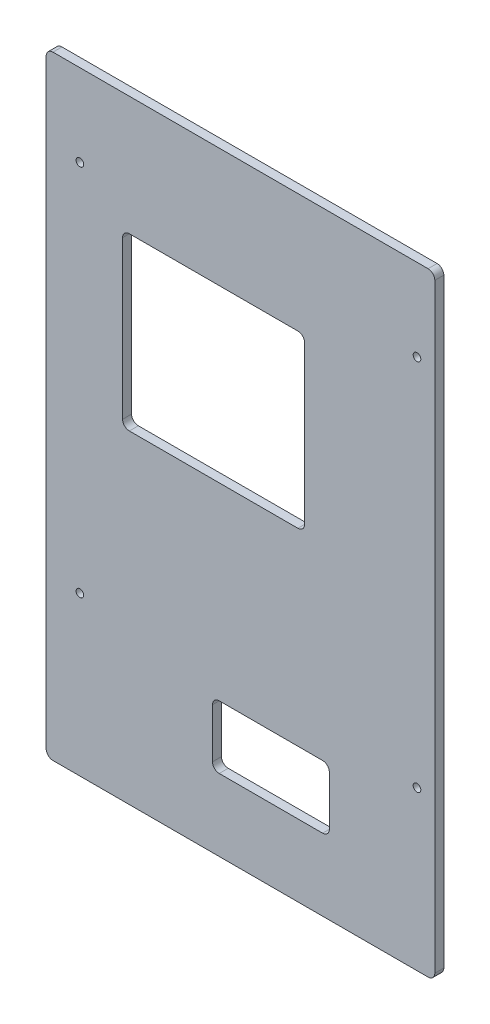
SolidWorks part; units mm, degrees
material "Verre"
ref_plane "Plan de face" through (0, 0, 0) normal (0, 0, 1) x (1, 0, 0)
ref_plane "Plan de dessus" through (0, 0, 0) normal (0, 1, 0) x (1, 0, 0)
ref_plane "Plan de droite" through (0, 0, 0) normal (1, 0, 0) x (0, 0, -1)
sketch "Esquisse1" plane through (0, 0, 0) normal (0, 0, 1) x (1, 0, 0)
  line L1 (0, 0) -> (172.93, 0)
  line L2 (0, 0) -> (0, 273)
  line L3 (0, 273) -> (172.93, 273)
  line L4 (172.93, 0) -> (172.93, 273)
  line L5 (74, 60) -> (126, 60)
  line L6 (74, 60) -> (74, 32)
  line L7 (74, 32) -> (126, 32)
  line L8 (126, 60) -> (126, 32)
  line L9 (34, 220) -> (115, 220)
  line L10 (34, 220) -> (34, 144)
  line L11 (34, 144) -> (115, 144)
  line L12 (115, 220) -> (115, 144)
  circle A0 centre (15, 236.5) radius 1.5
  circle A1 centre (165, 236.5) radius 1.5
  circle A2 centre (15, 70.5) radius 1.5
  circle A3 centre (165, 70.5) radius 1.5
  dimension "D5" = 3
  dimension "D8" = 3
  dimension "D11" = 3
  dimension "D22" = 3
  dimension "D1" = 172.93
  dimension "D2" = 273
  dimension "D3" = 36.5
  dimension "D4" = 15
  dimension "D6" = 7.93
  dimension "D7" = 36.5
  dimension "D9" = 70.5
  dimension "D10" = 15
  dimension "D12" = 74
  dimension "D13" = 52
  dimension "D14" = 28
  dimension "D15" = 32
  dimension "D16" = 34
  dimension "D17" = 81
  dimension "D18" = 144
  dimension "D19" = 76
  dimension "D20" = 7.93
  dimension "D21" = 70.5
extrude "Boss.-Extru.1" add sketch "Esquisse1" along normal blind 4
hole_wizard "Dégagement M31" positions "Esquisse2" profile "Esquisse3" hole size "M3" standard "ISO" end condition through all
sketch "Esquisse2" plane through (0, 0, 4) normal (0, 0, 1) x (1, 0, 0)
  point P0 (15, 236.5)
  point P3 (15, 70.5)
  point P6 (165, 236.5)
  point P9 (165, 70.5)
sketch "Esquisse3" plane through (15, 236.5, 4) normal (1, 0, 0) x (0, -1, 0)
  line L0 (0, 0) -> (0, 4)
  line L1 (0, 4) -> (1.7, 4)
  line L2 (1.7, 4) -> (1.7, 0)
  line L5 (1.7, 0) -> (0, 0)
  line L11 (0, -6.35) -> (0, 107.95) construction
  dimension "Diamètre du perçage jusqu'au prochain" = 3.4
  dimension "Profondeur du perçage jusqu'au prochain" = 4
fillet "Congé1" radius 3 12 edges at (0, 0, 2) (172.93, 0, 2) (126, 32, 2) (74, 32, 2) (126, 60, 2) (74, 60, 2) (115, 144, 2) (34, 144, 2) (115, 220, 2) (34, 220, 2) (172.93, 273, 2) (0, 273, 2)
